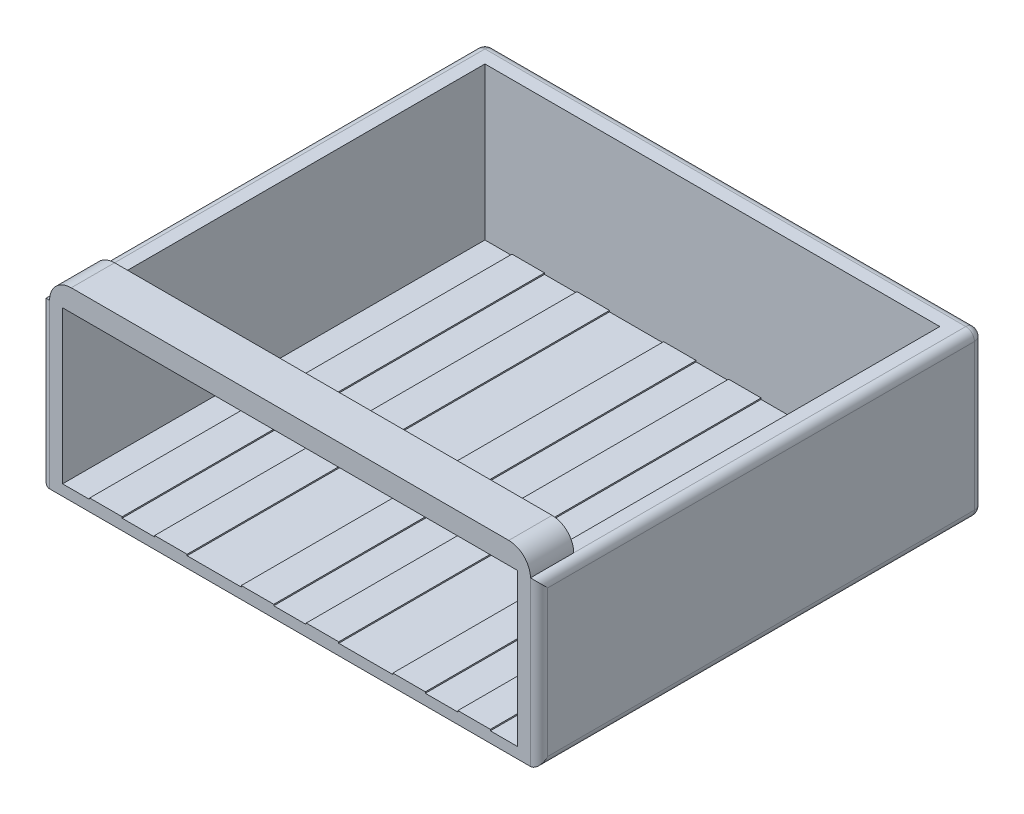
SolidWorks part; units mm, degrees
material "ABS"
ref_plane "Front Plane" through (0, 0, 0) normal (0, 0, 1) x (1, 0, 0)
ref_plane "Top Plane" through (0, 0, 0) normal (0, 1, 0) x (1, 0, 0)
ref_plane "Right Plane" through (0, 0, 0) normal (1, 0, 0) x (0, 0, -1)
sketch "Sketch1" plane through (0, 0, 0) normal (0, 1, 0) x (1, 0, 0)
  line L0 (-133.35, 123.825) -> (133.35, 123.825)
  line L1 (133.35, 123.825) -> (133.35, -123.825)
  line L2 (133.35, -123.825) -> (-133.35, -123.825)
  line L3 (-133.35, -123.825) -> (-133.35, 123.825)
  line L4 (-133.35, 123.825) -> (133.35, -123.825) construction
  line L5 (133.35, 123.825) -> (-133.35, -123.825) construction
  point P2 (0, 0)
  dimension "D1" = 266.7
  dimension "D2" = 247.65
extrude "Boss-Extrude1" add sketch "Sketch1" along normal blind 6.35
sketch "Sketch2" plane through (-133.35, 0, 0) normal (-1, 0, 0) x (0, 0, 1)
  line L0 (-123.825, 0) -> (-123.825, 95.758)
  line L1 (-123.825, 0) -> (123.825, 0)
  line L2 (123.825, 0) -> (123.825, 95.758)
  line L3 (123.825, 95.758) -> (-123.825, 95.758)
  dimension "D1" = 95.758
extrude "Boss-Extrude2" add sketch "Sketch2" along normal blind 12.7
mirror "Mirror1" about plane through (0, 0, 0) normal (1, 0, 0) of "Boss-Extrude2"
sketch "Sketch3" plane through (0, 0, -123.825) normal (0, 0, -1) x (-1, 0, 0)
  line L0 (-146.05, 0) -> (-146.05, 95.758)
  line L1 (-146.05, 95.758) -> (146.05, 95.758)
  line L2 (146.05, 95.758) -> (146.05, 0)
  line L3 (146.05, 0) -> (-146.05, 0)
extrude "Boss-Extrude3" add sketch "Sketch3" along normal blind 12.7
sketch "Sketch4" plane through (0, 6.35, 0) normal (0, 1, 0) x (1, 0, 0)
  line L0 (-117.475, 123.825) -> (-117.475, -123.825)
  line L1 (133.35, 123.825) -> (-133.35, 123.825) construction
  line L2 (-133.35, -123.825) -> (133.35, -123.825) construction
  line L3 (-117.475, -123.825) -> (-98.425, -123.825)
  line L4 (-98.425, -123.825) -> (-98.425, 123.825)
  line L5 (-98.425, 123.825) -> (-117.475, 123.825)
  line L6 (-133.35, -123.825) -> (-133.35, 123.825) construction
  line L7 (-79.375, 123.825) -> (-79.375, -123.825)
  line L8 (-133.35, 123.825) -> (133.35, 123.825) construction
  line L9 (-79.375, -123.825) -> (-60.325, -123.825)
  line L10 (-60.325, -123.825) -> (-60.325, 123.825)
  line L11 (-60.325, 123.825) -> (-79.375, 123.825)
  line L13 (-9.525, 123.825) -> (-28.575, 123.825)
  line L14 (-28.575, 123.825) -> (-28.575, -123.825)
  line L15 (-28.575, -123.825) -> (-9.525, -123.825)
  line L16 (-9.525, -123.825) -> (-9.525, 123.825)
  line L17 (28.575, 123.825) -> (9.525, 123.825)
  line L18 (9.525, 123.825) -> (9.525, -123.825)
  line L19 (9.525, -123.825) -> (28.575, -123.825)
  line L20 (28.575, -123.825) -> (28.575, 123.825)
  line L21 (79.375, 123.825) -> (60.325, 123.825)
  line L22 (60.325, 123.825) -> (60.325, -123.825)
  line L23 (60.325, -123.825) -> (79.375, -123.825)
  line L24 (79.375, -123.825) -> (79.375, 123.825)
  line L25 (117.475, 123.825) -> (98.425, 123.825)
  line L26 (98.425, 123.825) -> (98.425, -123.825)
  line L27 (98.425, -123.825) -> (117.475, -123.825)
  line L28 (117.475, -123.825) -> (117.475, 123.825)
  dimension "D1" = 15.875
  dimension "D2" = 19.05
  dimension "D3" = 19.05
  dimension "D4" = 19.05
  dimension "D5" = 3
  dimension "D6" = 31.75
extrude "Boss-Extrude4" add sketch "Sketch4" along normal blind 0.762 contours L4 L5 L0 L3
fillet "Fillet1" radius 5.08 10 edges at (-146.05, 0, -6.35) (-146.05, 47.879, 123.825) (-146.05, 95.758, -6.35) (146.05, 0, -6.35) (146.05, 95.758, -6.35) (146.05, 47.879, 123.825) (0, 0, -136.525) (-146.05, 47.879, -136.525) (0, 95.758, -136.525) (146.05, 47.879, -136.525)
sketch "Sketch6" plane through (0, 0, 123.825) normal (0, 0, 1) x (1, 0, 0)
  line L0 (-140.97, 95.758) -> (-140.97, 108.458)
  line L1 (-140.97, 108.458) -> (140.97, 108.458)
  line L2 (140.97, 108.458) -> (140.97, 95.758)
  line L3 (-140.97, 95.758) -> (140.97, 95.758)
  dimension "D1" = 12.7
extrude "Boss-Extrude5" add sketch "Sketch6" against normal blind 25.4
fillet "Fillet2" radius 12.7 2 edges at (140.97, 108.458, 111.125) (-140.97, 108.458, 111.125)
